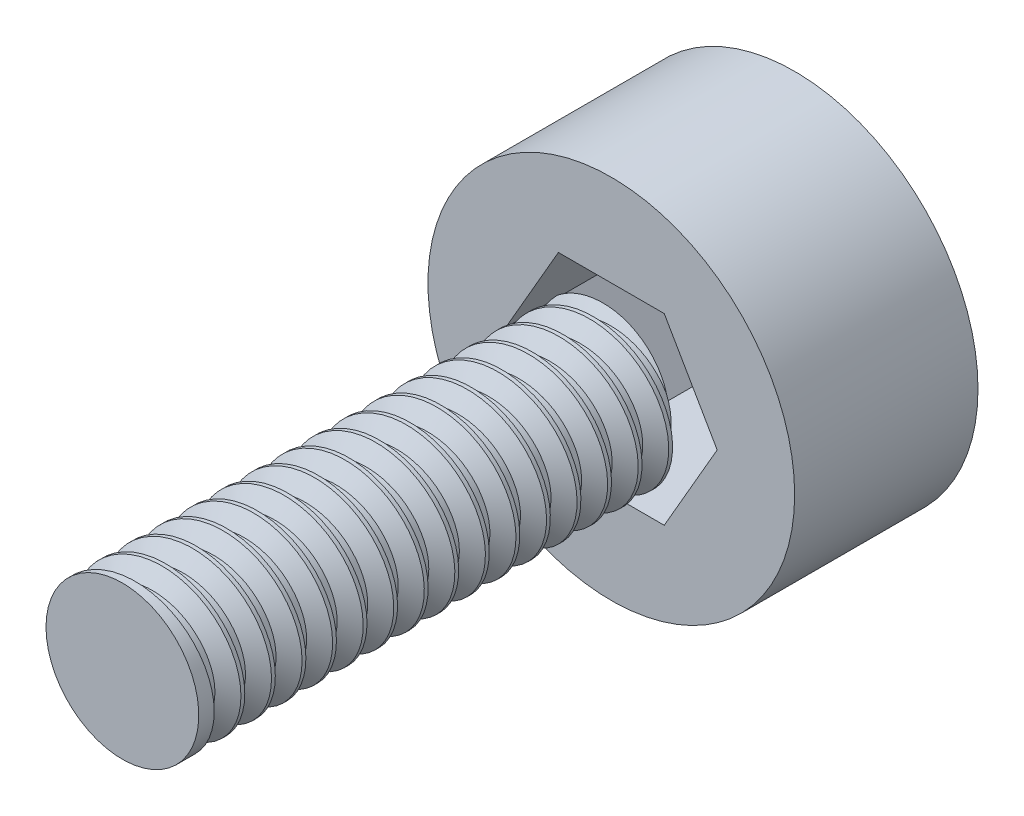
SolidWorks part; units mm, degrees
material "201 Annealed Stainless Steel (SS)"
ref_plane "Front Plane" through (0, 0, 0) normal (0, 0, 1) x (1, 0, 0)
ref_plane "Top Plane" through (0, 0, 0) normal (0, 1, 0) x (1, 0, 0)
ref_plane "Right Plane" through (0, 0, 0) normal (1, 0, 0) x (0, 0, -1)
sketch "Sketch1" plane through (0, 0, 0) normal (0, 0, 1) x (1, 0, 0)
  circle A0 centre (0, 0) radius 1.9844
  dimension "D1" = 3.9688
extrude "Boss-Extrude1" add sketch "Sketch1" along normal blind 12.7
thread "Thread1" pitch 0.7937 method cut profile "Thread Profile1" start angle 0, offset 0, length 0, pitch 0.7937, diameter 3.9688
ref_plane "Plane1" through (-1.9844, 0, 12.7) normal (0, -1, 0) x (-1, 0, 0)
sketch "Thread Profile1" plane through (-1.9844, 0, 12.7) normal (0, -1, 0) x (-1, 0, 0)
  line L0 (0, 0) -> (0, 0.7937) construction
  line L11 (0, 0) -> (0, 0.6945)
  line L12 (0, 0.6945) -> (-0.4296, 0.4465)
  line L13 (-0.4296, 0.4465) -> (-0.4296, 0.248)
  line L15 (-0.4296, 0.248) -> (0, 0)
  line L17 (-0.4296, 0.3473) -> (0, 0.3473) construction
  point P2 (0, 0)
  dimension "Pitch" = 0.7937
  dimension "Profile_Angle" = 60
  dimension "Profile_Land" = 0.1984
  dimension "Profile_Height" = 0.4296
sketch "Sketch6" plane through (0, 0, 0) normal (0, 0, 1) x (1, 0, 0)
  line L1 (2.7496, 0) -> (1.3748, 2.3813)
  line L2 (1.3748, 2.3813) -> (-1.3748, 2.3813)
  line L3 (-1.3748, 2.3813) -> (-2.7496, 0)
  line L4 (-2.7496, 0) -> (-1.3748, -2.3812)
  line L5 (-1.3748, -2.3812) -> (1.3748, -2.3812)
  line L6 (1.3748, -2.3812) -> (2.7496, 0)
  circle A0 centre (0, 0) radius 2.3812 construction
  circle A1 centre (0, 0) radius 4.7625
  dimension "D2" = 9.525
  dimension "D1" = 4.7625
extrude "Boss-Extrude2" add sketch "Sketch6" against normal blind 4.7625
